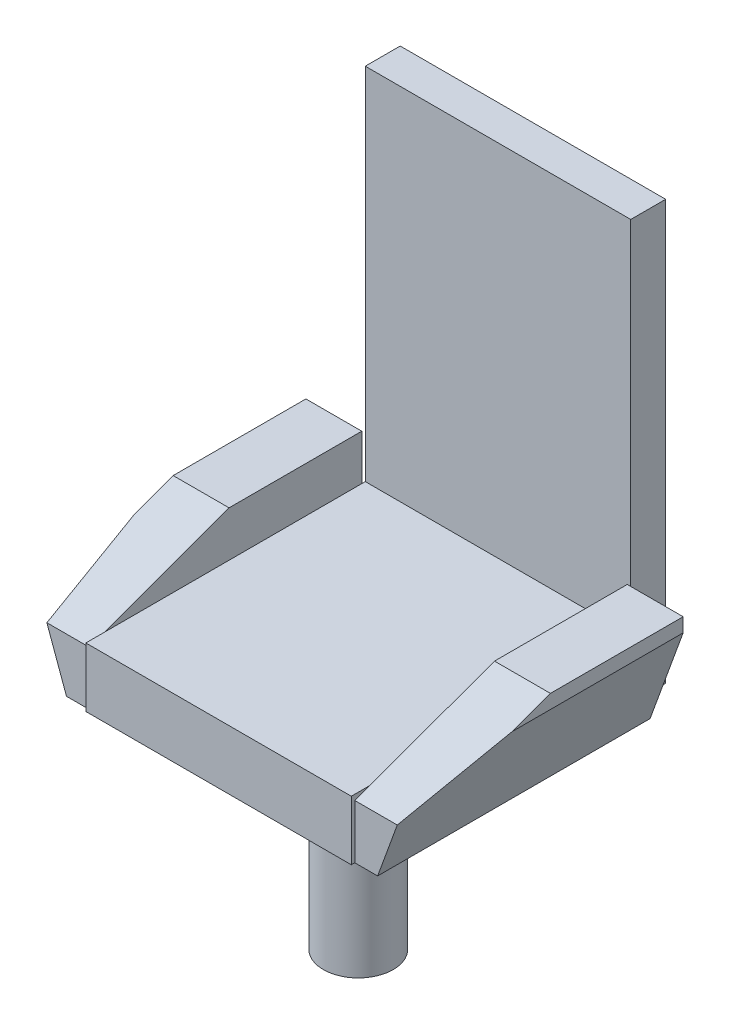
SolidWorks part; units mm, degrees
ref_plane "Front Plane" through (0, 0, 0) normal (0, 0, 1) x (1, 0, 0)
ref_plane "Top Plane" through (0, 0, 0) normal (0, 1, 0) x (1, 0, 0)
ref_plane "Right Plane" through (0, 0, 0) normal (1, 0, 0) x (0, 0, -1)
sketch "Sketch1" plane through (0, 0, 0) normal (0, 1, 0) x (1, 0, 0)
  line L1 (-190, -200) -> (190, -200)
  line L2 (-190, -200) -> (-190, 200)
  line L3 (-190, 200) -> (190, 200)
  line L4 (190, -200) -> (190, 200)
  line L5 (-190, -200) -> (190, 200) construction
  line L6 (-190, 200) -> (190, -200) construction
  point P0 (0, 0)
  dimension "D1" = 400
  dimension "D2" = 380
extrude "Boss-Extrude1" add sketch "Sketch1" along normal blind 85
sketch "Sketch2" plane through (0, 0, 0) normal (0, 1, 0) x (1, 0, 0)
  line L0 (190, -200) -> (190, 200) construction
  line L1 (-270, -195) -> (-190, -195)
  line L2 (-270, -195) -> (-270, 195)
  line L3 (-270, 195) -> (-190, 195)
  line L4 (270, -195) -> (270, 195)
  line L5 (-270, -195) -> (-190, -137.2222) construction
  line L6 (-270, 195) -> (-190, 137.2222) construction
  line L7 (190, 195) -> (270, 195)
  line L8 (190, 195) -> (190, -195)
  line L9 (190, -195) -> (270, -195)
  line L10 (270, 195) -> (270, -195)
  line L11 (190, 195) -> (270, 195)
  line L12 (-190, -195) -> (-270, -195)
  line L13 (-190, -195) -> (-190, 195)
  line L14 (-190, 195) -> (-270, 195)
  line L15 (-270, -195) -> (-270, 195)
  line L16 (190, -137.2222) -> (270, -195) construction
  line L17 (190, 137.2222) -> (270, 195) construction
  line L18 (190, -195) -> (270, -195)
  point P0 (0, 0)
  point P11 (0, 0)
  dimension "D1" = 540
  dimension "D2" = 390
extrude "Boss-Extrude2" add sketch "Sketch2" along normal blind 150 contours L1 L13 L3 L2 | L8 L9 L4 L7 region at (-230, 0, 0) region at (230, 0, 0)
chamfer "Chamfer1" distance 200 angle 20 2 edges at (-230, 150, 195) (230, 150, 195) first distance on face at (-230, 150, 0) first distance on face at (230, 150, 0)
chamfer "Chamfer2" distance 130 angle 20 2 edges at (270, 0, 0) (-270, 0, 0) first distance on face at (270, 75.4412, -1) first distance on face at (-270, 75.4412, -1)
sketch "Sketch3" plane through (0, 0, -200) normal (0, 0, -1) x (-1, 0, 0)
  line L1 (190, 0) -> (-190, 0)
  line L2 (190, 0) -> (190, 600)
  line L3 (190, 600) -> (-190, 600)
  line L4 (-190, 0) -> (-190, 600)
  dimension "D1" = 600
extrude "Boss-Extrude3" add sketch "Sketch3" along normal blind 50
sketch "Sketch4" plane through (0, 0, 0) normal (0, -1, 0) x (1, 0, 0)
  circle A0 centre (0, 0) radius 50
  dimension "D1" = 100
extrude "Boss-Extrude4" add sketch "Sketch4" along normal blind 300
